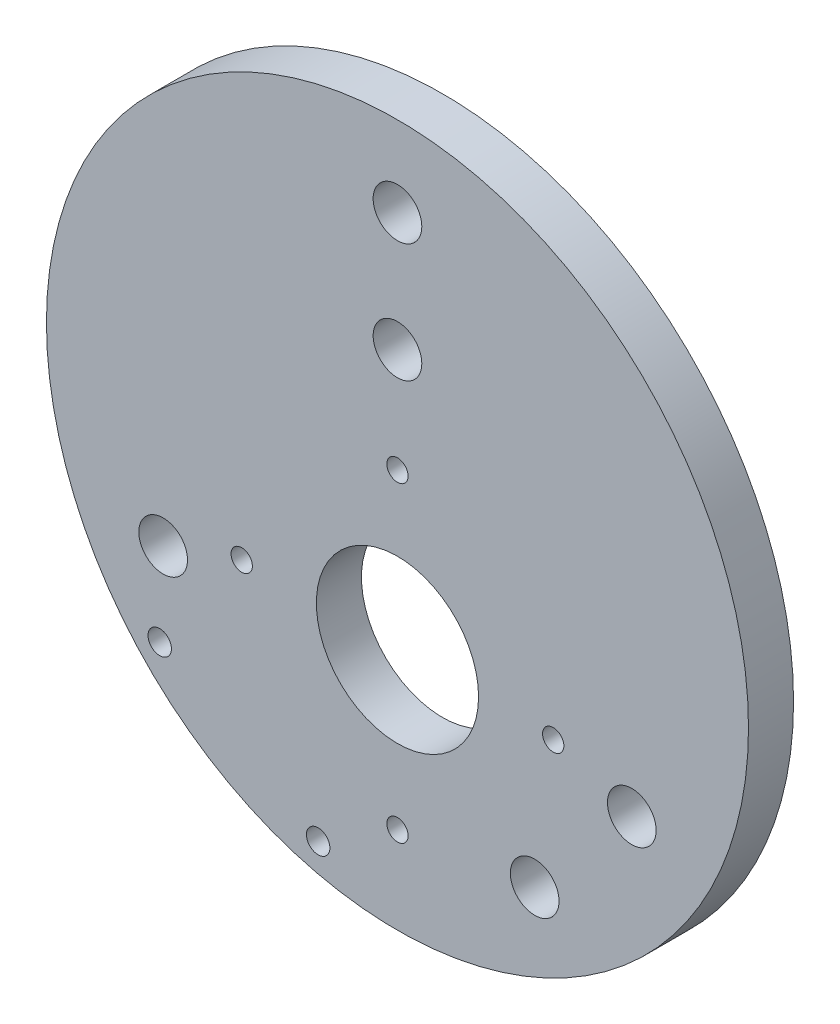
SolidWorks part; units mm, degrees
ref_plane "Front Plane" through (0, 0, 0) normal (0, 0, 1) x (1, 0, 0)
ref_plane "Top Plane" through (0, 0, 0) normal (0, 1, 0) x (1, 0, 0)
ref_plane "Right Plane" through (0, 0, 0) normal (1, 0, 0) x (0, 0, -1)
sketch "Sketch1" plane through (0, 0, 0) normal (0, 0, 1) x (1, 0, 0)
  circle A0 centre (0, 0) radius 49.4665
  dimension "D1" = 98.933
extrude "Boss-Extrude1" add sketch "Sketch1" along normal blind 6.35
sketch "Sketch2" plane through (0, 0, 6.35) normal (0, 0, 1) x (1, 0, 0)
  line L0 (0, -37.1877) -> (0, 6.7077) construction
  line L1 (-21.9477, -15.24) -> (0, 6.7077)
  line L2 (-21.9477, -15.24) -> (0, -37.1877)
  line L3 (0, -37.1877) -> (21.9477, -15.24)
  line L4 (0, 6.7077) -> (21.9477, -15.24)
  line L5 (0, -15.24) -> (12.0918, -15.24) construction
  point P4 (0, -15.24)
  dimension "D1" = 31.0388
  dimension "D2" = 31.0388
  dimension "D3" = 15.24
  dimension "D4" = 90
hole_wizard "M3 Screw Hole - Ø3.0mm Dowel Hole" positions "Sketch3" profile "Sketch4" hole size "Ø3.0" standard "ANSI Metric" end condition through all
sketch "Sketch3" plane through (0, 0, 6.35) normal (0, 0, 1) x (1, 0, 0)
  point P0 (0, 6.7077)
  point P3 (-21.9477, -15.24)
  point P6 (0, -37.1877)
  point P9 (21.9477, -15.24)
sketch "Sketch4" plane through (0, 6.7077, 6.35) normal (1, 0, 0) x (0, -1, 0)
  line L0 (0, 0) -> (0, 6.35)
  line L1 (0, 6.35) -> (1.5, 6.35)
  line L2 (1.5, 6.35) -> (1.5, 0)
  line L5 (1.5, 0) -> (0, 0)
  line L11 (0, -6.35) -> (0, 107.95) construction
  dimension "Thru Hole Dia." = 3
  dimension "Thru Hole Depth" = 6.35
sketch "Sketch5" plane through (0, 0, 6.35) normal (0, 0, 1) x (1, 0, 0)
  line L0 (0, -37.1877) -> (0, 6.7077) construction
  line L1 (-29.9941, -15.24) -> (0, 14.7541)
  line L2 (-29.9941, -15.24) -> (0, -45.2341)
  line L3 (0, -45.2341) -> (29.9941, -15.24)
  line L4 (0, 14.7541) -> (29.9941, -15.24)
  line L5 (-29.9941, -15.24) -> (29.9941, -15.24) construction
  line L6 (0, -45.2341) -> (0, 14.7541) construction
  line L7 (-19.3974, 4.1574) -> (0, -15.24) construction
  line L8 (0, -15.24) -> (19.3974, -15.24) construction
  line L9 (0, -15.24) -> (19.3974, -34.6374) construction
  line L10 (0, -15.24) -> (-3.0533, -18.2933) construction
  line L11 (-3.0533, -18.2933) -> (16.3441, -37.6906) construction
  line L12 (0, -15.24) -> (-19.3974, -34.6374) construction
  line L13 (0, -15.24) -> (-18.3197, 3.0797) construction
  line L14 (-18.3197, 3.0797) -> (0, 21.3994) construction
  circle A0 centre (0, 21.3994) radius 3.429
  circle A1 centre (16.3441, -37.6906) radius 3.429
  circle A2 centre (-19.3974, -34.6374) radius 3.429
  point P0 (0, -15.24)
  point P7 (0, -15.24)
  dimension "D3" = 27.432
  dimension "D5" = 27.432
  dimension "D9" = 6.858
  dimension "D1" = 42.418
  dimension "D2" = 4.318
  dimension "D4" = 42.418
  dimension "D6" = 27.432
  dimension "D7" = 135
  dimension "D8" = 25.908
sketch "Sketch6" plane through (0, 0, 6.35) normal (0, 0, 1) x (1, 0, 0)
  line L0 (0, 38.1282) -> (-33.02, -19.0641) construction
  line L1 (-33.02, -19.0641) -> (33.02, -19.0641) construction
  line L2 (33.02, -19.0641) -> (0, 38.1282) construction
  line L3 (-33.02, -19.0641) -> (0, 0) construction
  line L4 (0, 0) -> (33.02, -19.0641) construction
  line L5 (0, 0) -> (0, 38.1282) construction
  circle A0 centre (0, 38.1282) radius 3.429
  circle A1 centre (-33.02, -19.0641) radius 3.429
  circle A2 centre (33.02, -19.0641) radius 3.429
  dimension "D1" = 6.858
  dimension "D2" = 66.04
  dimension "D3" = 60
  dimension "D4" = 60
extrude "Cut-Extrude2" cut sketch "Sketch6" against normal through all
sketch "Sketch7" plane through (0, 0, 6.35) normal (0, 0, 1) x (1, 0, 0)
  line L0 (0, -37.1877) -> (0, 6.7077) construction
  circle A0 centre (0, -15.24) radius 11.43
  point P4 (0, -15.24)
  dimension "D1" = 22.86
extrude "Cut-Extrude3" cut sketch "Sketch7" against normal through all
sketch "Possible Plate Hole Reference" plane through (0, 0, 6.35) normal (0, 0, 1) x (1, 0, 0)
  line L0 (47.781, 12.8029) -> (-47.781, -12.8029) construction
  line L1 (0, 0) -> (49.4665, 0) construction
  circle A0 centre (0, 0) radius 49.4665 construction
  circle A1 centre (0, 0) radius 4.9466 construction
  circle A2 centre (0, 0) radius 49.4665 construction
  point P7 (0, 0)
  dimension "D2" = 9.8933
  dimension "D3" = 98.933
  dimension "D1" = 15
extrude "Cut-Extrude4" cut sketch "Sketch5" against normal through all contours A0 region at (0, 21.3994, 6.35)
sketch "Sketch11" plane through (0, 0, 6.35) normal (0, 0, 1) x (1, 0, 0)
  line L0 (0, 21.3994) -> (0, -59.7695) construction
  line L1 (0, 21.3994) -> (-33.5025, -31.0425) construction
  line L2 (-33.5025, -31.0425) -> (-11.176, -44.1861) construction
  line L3 (-11.176, -44.1861) -> (0, -44.1861) construction
  line L4 (0, 21.3994) -> (19.3378, -34.5341) construction
  line L5 (19.3378, -34.5341) -> (0, -34.5341) construction
  circle A0 centre (19.3378, -34.5341) radius 3.429
  circle A1 centre (-11.176, -44.1861) radius 1.651
  circle A2 centre (-33.5025, -31.0425) radius 1.651
  circle A3 centre (0, 21.3994) radius 3.429 construction
  point P6 (0, 0)
  point P14 (0, 0)
  point P15 (0, 0)
  dimension "D1" = 3.302
  dimension "D2" = 6.858
  dimension "D3" = 62.23
  dimension "D4" = 25.908
  dimension "D5" = 11.176
  dimension "D6" = 59.182
  dimension "D7" = 9.652
  dimension "D8" = 32.004
  dimension "D9" = 32.572
extrude "Cut-Extrude7" cut sketch "Sketch11" against normal through all
equation "\"D2@Possible Plate Hole Reference\" = 0.1 * \"D3@Possible Plate Hole Reference\""
